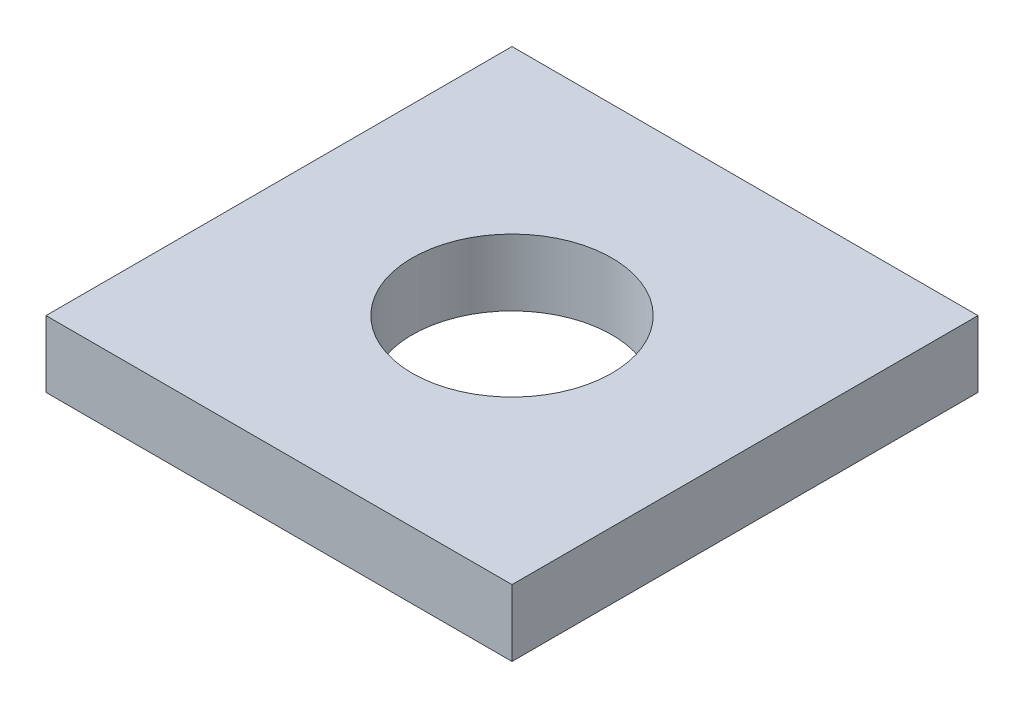
SolidWorks part; units mm, degrees
ref_plane "前视基准面" through (0, 0, 0) normal (0, 0, 1) x (1, 0, 0)
ref_plane "上视基准面" through (0, 0, 0) normal (0, 1, 0) x (1, 0, 0)
ref_plane "右视基准面" through (0, 0, 0) normal (1, 0, 0) x (0, 0, -1)
other "Configuration Table"
sketch "草图1" plane through (0, 0, 0) normal (0, 1, 0) x (1, 0, 0)
  line L7 (-3.5, 3.5) -> (3.5, 3.5)
  line L8 (-3.5, 3.5) -> (-3.5, -3.5)
  line L9 (-3.5, -3.5) -> (3.5, -3.5)
  line L10 (3.5, 3.5) -> (3.5, -3.5)
  line L11 (-3.5, 3.5) -> (3.5, -3.5) construction
  line L12 (-3.5, -3.5) -> (3.5, 3.5) construction
  circle A0 centre (0, 0) radius 1.5
  point P0 (0, 0)
  point P5 (0, 0)
  dimension "D1" = 3
  dimension "D4" = 7
extrude "凸台-拉伸1" add sketch "草图1" along normal blind 1 contours L9 L10 L7 L8 | A0
